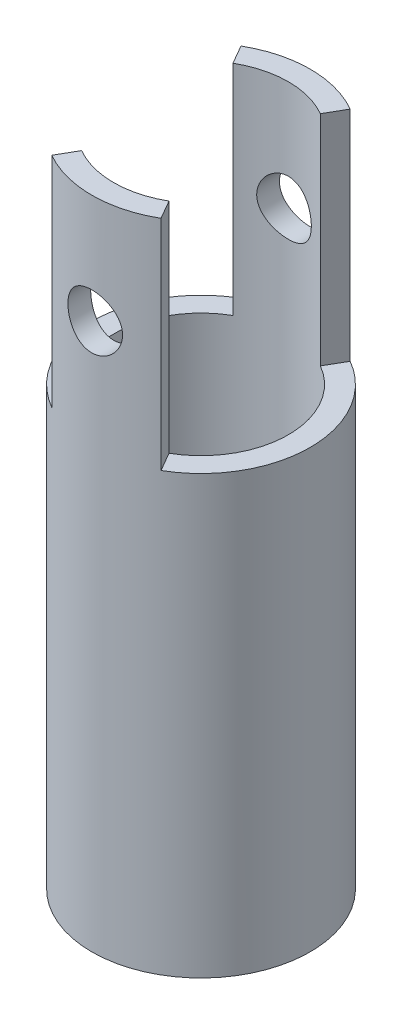
SolidWorks part; units mm, degrees
ref_plane "Front Plane" through (0, 0, 0) normal (0, 0, 1) x (1, 0, 0)
ref_plane "Top Plane" through (0, 0, 0) normal (0, 1, 0) x (1, 0, 0)
ref_plane "Right Plane" through (0, 0, 0) normal (1, 0, 0) x (0, 0, -1)
sketch "草图1" plane through (0, 0, 0) normal (0, 1, 0) x (1, 0, 0)
  circle A0 centre (0, 0) radius 1
  circle A1 centre (0, 0) radius 0.8
extrude "凸台-拉伸1" add sketch "草图1" along normal blind 6
sketch "草图2" plane through (0, 6, 0) normal (0, 1, 0) x (1, 0, 0)
  line L1 (-0.5, 0.866) -> (0, 0)
  line L2 (0, 0) -> (0.5, -0.866)
  line L3 (-0.5, -0.866) -> (0, 0)
  line L5 (0.5, 0.866) -> (0, 0)
  line L6 (0, 0) -> (-0.5, -0.866)
  line L7 (0.5, -0.866) -> (0, 0)
  circle A0 centre (0, 0) radius 1 construction
  arc A3 (-0.5, 0.866) -> (-0.5, -0.866) centre (0, 0) ccw
  arc A4 (0.5, -0.866) -> (0.5, 0.866) centre (0, 0) ccw
  circle M12 centre (0, 0) radius 1
  circle M13 centre (0, 0) radius 0.8
extrude "切除-拉伸2" cut sketch "草图2" against normal blind 2 contours L5 L2 M13 | L3 L1 M13 | L3 L1 M12 M13 | L5 L2 M12 M13 region at (-0.4659, 6, -0.7703) region at (-0.4411, 6, 0) region at (0.8502, 6, -0.4908) region at (0.4411, 6, 0)
sketch "草图4" plane through (0, 0, 0) normal (0, 0, 1) x (1, 0, 0)
  line L0 (-0.5, 6) -> (0.5, 4)
  line L1 (0.5, 4) -> (0.5, 6)
  line L2 (0.5, 6) -> (-0.5, 4)
  line L3 (-0.5, 4) -> (-0.5, 6) construction
  circle A0 centre (0, 5) radius 0.25
extrude "切除-拉伸3" cut sketch "草图4" against normal blind 2 and the other way blind 2 contours L0 A0 L2 | L2 A0 L0 | L0 A0 L2 | L2 A0 L0 region at (0, 5.1608, 0) region at (-0.1346, 5, 0) region at (0.1346, 5, 0) region at (0, 4.8392, 0)
sketch "草图5" plane through (0, 0, 0) normal (0, 0, 1) x (1, 0, 0)
  line L1 (-0.3, 4.7) -> (0.3, 4.7)
  line L2 (-0.3, 4.7) -> (-0.3, 5.3)
  line L3 (-0.3, 5.3) -> (0.3, 5.3)
  line L4 (0.3, 4.7) -> (0.3, 5.3)
  line L5 (0, 5.3) -> (0, 4.7) construction
  line L6 (-0.3, 5) -> (0.3, 5) construction
  point P0 (0, 5)
